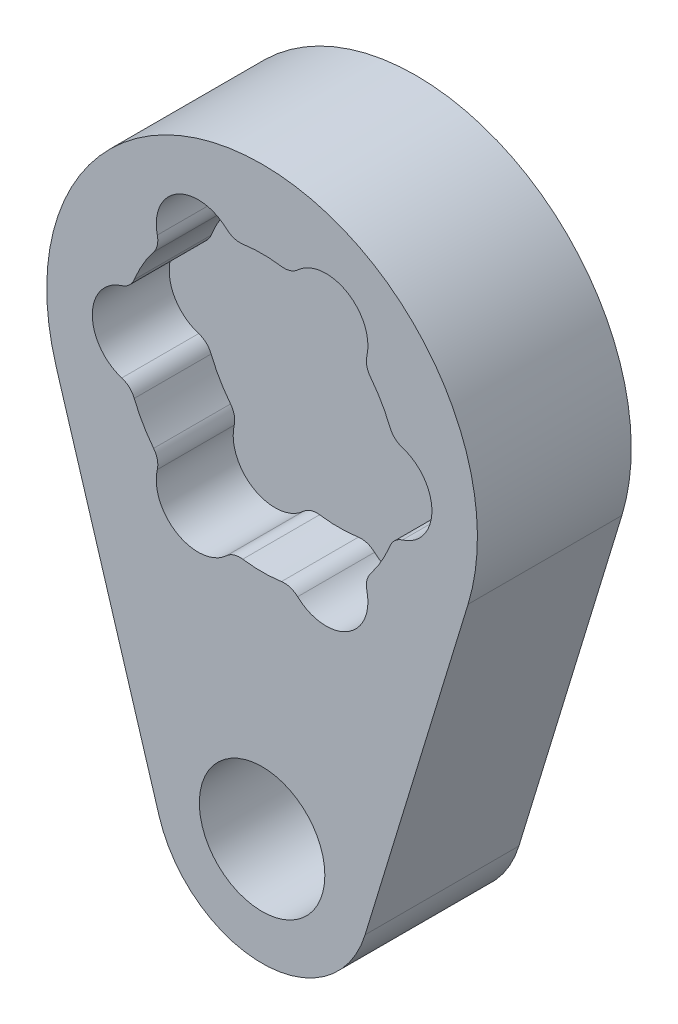
SolidWorks part; units mm, degrees
ref_plane "Front Plane" through (0, 0, 0) normal (0, 0, 1) x (1, 0, 0)
ref_plane "Top Plane" through (0, 0, 0) normal (0, 1, 0) x (1, 0, 0)
ref_plane "Right Plane" through (0, 0, 0) normal (1, 0, 0) x (0, 0, -1)
sketch "Sketch1" plane through (0, 0, 0) normal (0, 0, 1) x (1, 0, 0)
  line L1 (-21.2587, -6.4823) -> (-10.6293, -41.3411)
  line L2 (21.2587, -6.4823) -> (10.6293, -41.3411)
  circle A1 centre (0, 0) radius 14.224
  circle A2 centre (-6.604, 11.4385) radius 4.318
  circle A3 centre (6.604, 11.4385) radius 4.318
  circle A4 centre (13.208, 0) radius 4.318
  circle A5 centre (6.604, -11.4385) radius 4.318
  circle A6 centre (-6.604, -11.4385) radius 4.318
  circle A7 centre (-13.208, 0) radius 4.318
  circle A8 centre (0, 0) radius 22.225
  circle A9 centre (0, -38.1) radius 6.477
  circle A10 centre (0, -38.1) radius 11.1125
  point P18 (0, 0)
  point P23 (-10.4207, -41.9597)
  point P25 (10.7829, -40.7863)
  dimension "D1" = 44.45
  dimension "D2" = 28.448
  dimension "D4" = 8.636
  dimension "D7" = 12.954
  dimension "D9" = 22.225
  dimension "D3" = 13.208
  dimension "D8" = 38.1
  dimension "D5" = 6
extrude "Boss-Extrude1" add sketch "Sketch1" along normal mid plane 15.875 contours A8 A7 A1 A2 A3 A4 A5 A6 | A8 L1 | A8 L2 | A10 A9 | A7 A1 A6 A5 A4 A3 A2 | A1 A7 | A1 A2 | A1 A2 | A1 A3 | A1 A3 | A1 A4 | A1 A4 | A1 A5 | A1 A5 | A1 A6 | A1 A6 | A1 A7 region at (0, -24.604, 0) region at (-3.1843, 21.3603, 0) region at (-1.5921, -27.4198, 0) region at (11.8032, 0, 0) region at (15.4718, 0, 0) region at (0, 0, 0) region at (5.9016, 10.2219, 0) region at (7.7359, 13.3989, 0) region at (7.7359, -13.3989, 0) region at (5.9016, -10.2219, 0) region at (-5.9016, 10.2219, 0) region at (-7.7359, 13.3989, 0) region at (-7.7359, -13.3989, 0) region at (-5.9016, -10.2219, 0) region at (-11.8032, 0, 0) region at (-15.4718, 0, 0)
extrude "Cut-Extrude1" cut sketch "Sketch1<3>" against normal blind 7.9375 from surface contours A7 A1 A6 A5 A4 A3 A2 | A1 A2 | A1 A2 | A1 A3 | A1 A3 | A1 A4 | A1 A4 | A1 A5 | A1 A5 | A1 A6 | A1 A6 | A1 A7 | A1 A7 region at (11.8032, 0, 0) region at (15.4718, 0, 0) region at (0, 0, 0) region at (5.9016, 10.2219, 0) region at (7.7359, 13.3989, 0) region at (7.7359, -13.3989, 0) region at (5.9016, -10.2219, 0) region at (-5.9016, 10.2219, 0) region at (-7.7359, 13.3989, 0) region at (-7.7359, -13.3989, 0) region at (-5.9016, -10.2219, 0) region at (-11.8032, 0, 0) region at (-15.4718, 0, 0) starting at face at (0, -18.7027, 7.9375)
sketch "Sketch1<3>" plane through (0, 0, 0) normal (0, 0, 1) x (1, 0, 0) same geometry as "Sketch1"
fillet "Fillet4" radius 2.032 12 edges at (-10.5059, 9.589, 3.9688) (-13.5573, 4.3039, 3.9688) (-10.5059, -9.589, 3.9688) (-3.0514, -13.8928, 3.9688) (3.0514, -13.8928, 3.9688) (10.5059, -9.589, 3.9688) (13.5572, -4.3039, 3.9688) (13.5572, 4.3039, 3.9688) (10.5059, 9.589, 3.9688) (3.0514, 13.8928, 3.9688) (-3.0514, 13.8928, 3.9688) (-13.5572, -4.3039, 3.9688)
